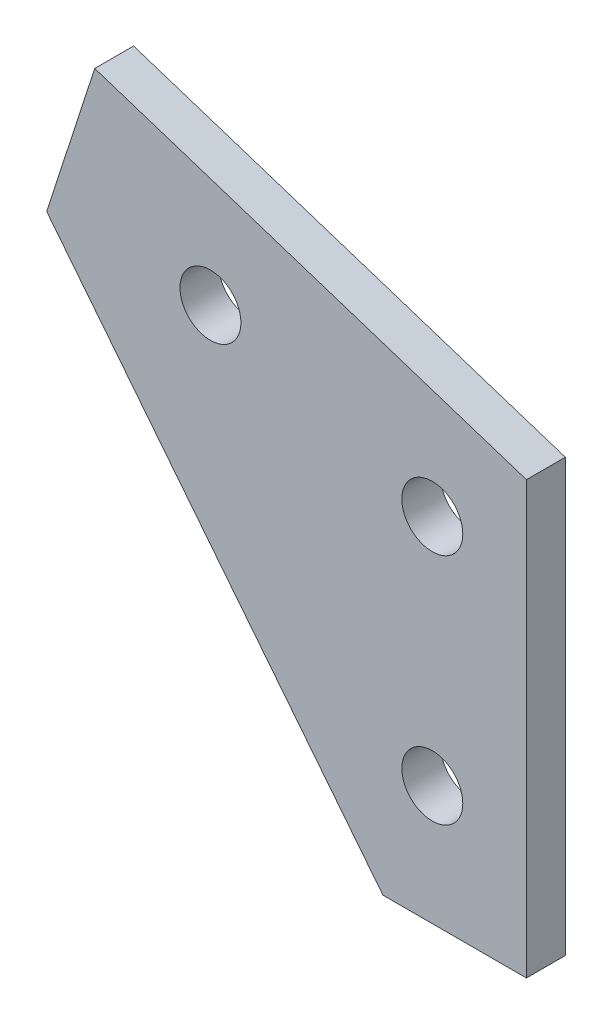
SolidWorks part; units mm, degrees
ref_plane "Front Plane" through (0, 0, 0) normal (0, 0, 1) x (1, 0, 0)
ref_plane "Top Plane" through (0, 0, 0) normal (0, 1, 0) x (1, 0, 0)
ref_plane "Right Plane" through (0, 0, 0) normal (1, 0, 0) x (0, 0, -1)
sketch "Sketch4" plane through (0, 0, 0) normal (0, 0, 1) x (1, 0, 0)
  line L0 (-40.992, 298.8407) -> (-42.1889, 295.1567) construction
  line L1 (-40.992, 298.8407) -> (-52.5693, 263.2093) construction
  line L2 (-42.1889, 295.1567) -> (-6.9331, 283.7014)
  line L3 (-42.1889, 295.1567) -> (-46.1134, 283.0783)
  line L4 (-6.9331, 283.7014) -> (-6.9331, 248.4582)
  line L5 (-6.9331, 248.4582) -> (-18.6537, 248.4582)
  line L6 (-18.6537, 248.4582) -> (-46.1134, 283.0783)
  dimension "D1" = 3.8735
extrude "Boss-Extrude1" add sketch "Sketch4" along normal blind 3.175
hole_wizard "#10 Clearance Hole1" positions "Sketch5" profile "Sketch6" hole size "#10" standard "ANSI Inch" end condition through all
sketch "Sketch5" plane through (0, 0, 3.175) normal (0, 0, 1) x (1, 0, 0)
  point P0 (-32.7403, 283.1387)
  point P3 (-14.6226, 277.2519)
  point P6 (-14.6226, 258.2019)
sketch "Sketch6" plane through (-32.7403, 283.1387, 3.175) normal (1, 0, 0) x (0, -1, 0)
  line L0 (0, 0) -> (0, 3.175)
  line L1 (0, 3.175) -> (2.4892, 3.175)
  line L2 (2.4892, 3.175) -> (2.4892, 0)
  line L5 (2.4892, 0) -> (0, 0)
  line L11 (0, -6.35) -> (0, 107.95) construction
  dimension "Thru Hole Dia." = 4.9784
  dimension "Thru Hole Depth" = 3.175
